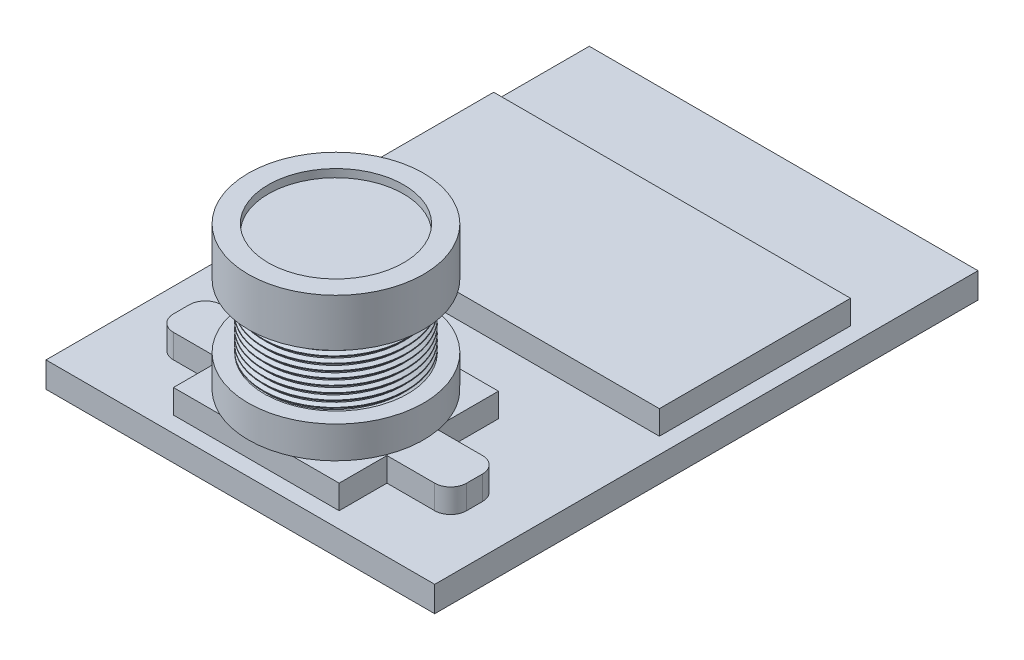
SolidWorks part; units mm, degrees
ref_plane "Front Plane" through (0, 0, 0) normal (0, 0, 1) x (1, 0, 0)
ref_plane "Top Plane" through (0, 0, 0) normal (0, 1, 0) x (1, 0, 0)
ref_plane "Right Plane" through (0, 0, 0) normal (1, 0, 0) x (0, 0, -1)
sketch "Sketch1" plane through (0, 0, 0) normal (0, 0, 1) x (1, 0, 0)
  line L1 (-14.1632, 2.419) -> (10.2368, 2.419)
  line L2 (-14.1632, 2.419) -> (-14.1632, 0.819)
  line L3 (-14.1632, 0.819) -> (10.2368, 0.819)
  line L4 (10.2368, 2.419) -> (10.2368, 0.819)
  dimension "D1" = 24.4
  dimension "D2" = 1.6
extrude "Boss-Extrude1" add sketch "Sketch1" along normal blind 34.1
sketch "Sketch2" plane through (0, 2.419, 0) normal (0, 1, 0) x (1, 0, 0)
  line L0 (10.2368, -34.1) -> (-14.1632, -34.1) construction
  line L1 (3.2368, -33.1) -> (-7.1632, -33.1)
  line L2 (3.2368, -33.1) -> (3.2368, -23.1)
  line L3 (3.2368, -23.1) -> (-7.1632, -23.1)
  line L4 (-7.1632, -33.1) -> (-7.1632, -23.1)
  line L5 (-14.1632, -34.1) -> (-14.1632, 0) construction
  line L6 (10.2368, -34.1) -> (10.2368, 0) construction
  dimension "D1" = 1
  dimension "D2" = 7
  dimension "D3" = 7
  dimension "D4" = 10
extrude "Boss-Extrude2" add sketch "Sketch2" along normal blind 1.5
sketch "Sketch3" plane through (0, 3.919, 0) normal (0, 1, 0) x (1, 0, 0)
  line L0 (10.2368, -34.1) -> (10.2368, 0) construction
  line L1 (7.2368, -30.1) -> (-11.1632, -30.1)
  line L2 (7.2368, -30.1) -> (7.2368, -27.1)
  line L3 (7.2368, -27.1) -> (-11.1632, -27.1)
  line L4 (-11.1632, -30.1) -> (-11.1632, -27.1)
  line L5 (-14.1632, -34.1) -> (-14.1632, 0) construction
  line L6 (10.2368, -34.1) -> (-14.1632, -34.1) construction
  dimension "D1" = 3
  dimension "D2" = 3
  dimension "D3" = 4
  dimension "D4" = 3
extrude "Boss-Extrude3" add sketch "Sketch3" against normal blind 1.5
fillet "Fillet1" radius 1 4 edges at (7.2368, 3.169, 30.1) (7.2368, 3.169, 27.1) (-11.1632, 3.169, 30.1) (-11.1632, 3.169, 27.1)
sketch "Sketch4" plane through (0, 3.919, 0) normal (0, 1, 0) x (1, 0, 0)
  line L0 (-7.1632, -30.1) -> (-7.1632, -33.1) construction
  line L1 (-7.1632, -33.1) -> (3.2368, -33.1) construction
  circle A0 centre (-1.9632, -28.1) radius 5.5
  dimension "D1" = 5.2
  dimension "D2" = 5
  dimension "D3" = 11
extrude "Boss-Extrude4" add sketch "Sketch4" along normal blind 2
sketch "Sketch5" plane through (0, 5.919, 0) normal (0, 1, 0) x (1, 0, 0)
  circle A0 centre (-1.9632, -28.1) radius 4.5
  dimension "D1" = 9
extrude "Boss-Extrude5" add sketch "Sketch5" along normal blind 4
thread "Thread1" pitch 0.4 method cut profile "Thread Profile1" start angle 0, offset 0, length 0, pitch 0.4, diameter 9
ref_plane "Plane1" through (-6.4632, 9.919, 28.1) normal (0, 0, 1) x (-1, 0, 0)
sketch "Thread Profile1" plane through (-6.4632, 9.919, 28.1) normal (0, 0, 1) x (-1, 0, 0)
  line L0 (0, 0) -> (0, 0.4) construction
  line L11 (0, 0) -> (0, 0.35)
  line L12 (0, 0.35) -> (-0.2165, 0.225)
  line L13 (-0.2165, 0.225) -> (-0.2165, 0.125)
  line L15 (-0.2165, 0.125) -> (0, 0)
  line L17 (-0.2165, 0.175) -> (0, 0.175) construction
  point P2 (0, 0)
  dimension "Pitch" = 0.4
  dimension "Profile_Angle" = 60
  dimension "Profile_Land" = 0.1
  dimension "Profile_Height" = 0.2165
sketch "Sketch9" plane through (0, 9.919, 0) normal (0, 1, 0) x (1, 0, 0)
  circle A0 centre (-1.9632, -28.1) radius 5.5
  dimension "D1" = 11
extrude "Boss-Extrude6" add sketch "Sketch9" along normal blind 3
sketch "Sketch11" plane through (0, 12.919, 0) normal (0, 1, 0) x (1, 0, 0)
  circle A0 centre (-1.9632, -28.1) radius 4.2466
extrude "Cut-Extrude1" cut sketch "Sketch11" against normal blind 0.5
sketch "Sketch12" plane through (0, 2.419, 0) normal (0, 1, 0) x (1, 0, 0)
  line L0 (-14.1632, -34.1) -> (-14.1632, 0) construction
  line L1 (9.2368, -19) -> (-13.1632, -19)
  line L2 (9.2368, -19) -> (9.2368, -7)
  line L3 (9.2368, -7) -> (-13.1632, -7)
  line L4 (-13.1632, -19) -> (-13.1632, -7)
  line L5 (10.2368, 0) -> (-14.1632, 0) construction
  dimension "D1" = 22.4
  dimension "D2" = 1
  dimension "D3" = 7
  dimension "D4" = 12
extrude "Boss-Extrude7" add sketch "Sketch12" along normal blind 1.5
sketch "Sketch13" plane through (0, 0.819, 0) normal (0, -1, 0) x (1, 0, 0)
  line L0 (-14.1632, 34.1) -> (-14.1632, 0) construction
  line L1 (-11.9632, 26.1) -> (8.0368, 26.1)
  line L2 (-11.9632, 26.1) -> (-11.9632, 6.1)
  line L3 (-11.9632, 6.1) -> (8.0368, 6.1)
  line L4 (8.0368, 26.1) -> (8.0368, 6.1)
  line L5 (-14.1632, 34.1) -> (10.2368, 34.1) construction
  dimension "D1" = 20
  dimension "D2" = 2.2
  dimension "D3" = 20
  dimension "D4" = 8
extrude "Boss-Extrude8" add sketch "Sketch13" along normal blind 1.5
